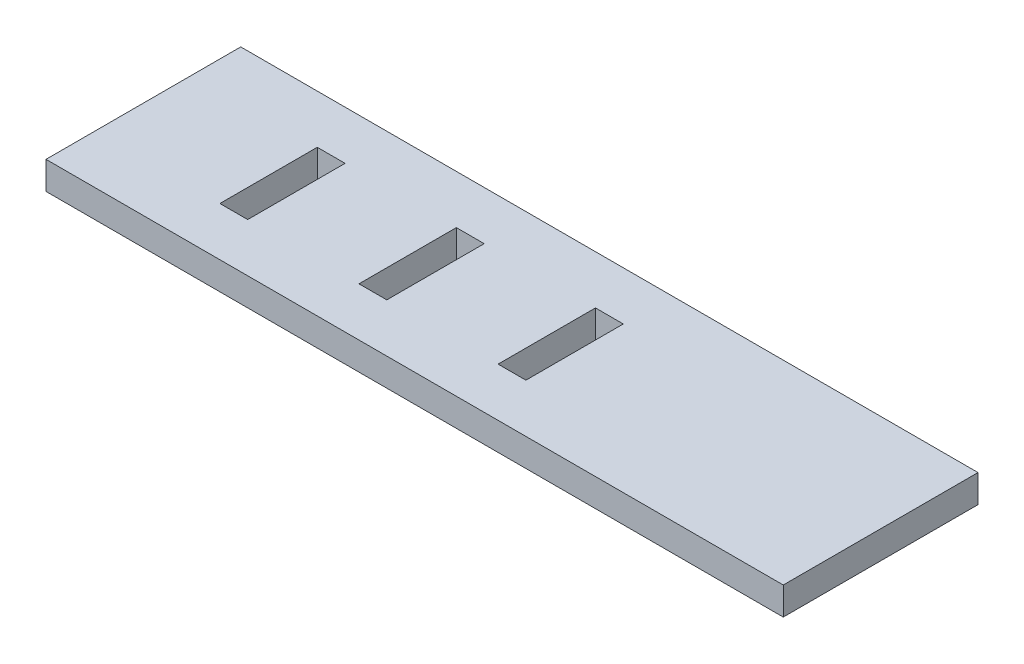
SolidWorks part; units mm, degrees
ref_plane "Front Plane" through (0, 0, 0) normal (0, 0, 1) x (1, 0, 0)
ref_plane "Top Plane" through (0, 0, 0) normal (0, 1, 0) x (1, 0, 0)
ref_plane "Right Plane" through (0, 0, 0) normal (1, 0, 0) x (0, 0, -1)
sketch "Sketch1" plane through (0, 0, 0) normal (0, 1, 0) x (1, 0, 0)
  line L0 (-98.4247, 5.9932) -> (-48.4247, 5.9932) construction
  line L1 (-98.4247, 40.9932) -> (166.5753, 40.9932)
  line L2 (-98.4247, 40.9932) -> (-98.4247, -29.0068)
  line L3 (-98.4247, -29.0068) -> (166.5753, -29.0068)
  line L4 (166.5753, 40.9932) -> (166.5753, -29.0068)
  line L5 (-98.4247, 5.9932) -> (1.5753, 5.9932) construction
  line L6 (-53.4247, 23.4932) -> (-43.4247, 23.4932)
  line L7 (-53.4247, 23.4932) -> (-53.4247, -11.5068)
  line L8 (-53.4247, -11.5068) -> (-43.4247, -11.5068)
  line L9 (-43.4247, 23.4932) -> (-43.4247, -11.5068)
  line L10 (-53.4247, 23.4932) -> (-43.4247, -11.5068) construction
  line L11 (-53.4247, -11.5068) -> (-43.4247, 23.4932) construction
  line L12 (-98.4247, 5.9932) -> (54.9772, 5.9932) construction
  line L13 (6.5753, 23.4932) -> (-3.4247, 23.4932)
  line L14 (6.5753, 23.4932) -> (6.5753, -11.5068)
  line L15 (6.5753, -11.5068) -> (-3.4247, -11.5068)
  line L16 (-3.4247, 23.4932) -> (-3.4247, -11.5068)
  line L17 (6.5753, 23.4932) -> (-3.4247, -11.5068) construction
  line L18 (6.5753, -11.5068) -> (-3.4247, 23.4932) construction
  line L21 (46.5753, 23.4932) -> (56.5753, 23.4932)
  line L22 (46.5753, 23.4932) -> (46.5753, -11.5068)
  line L23 (46.5753, -11.5068) -> (56.5753, -11.5068)
  line L24 (56.5753, 23.4932) -> (56.5753, -11.5068)
  line L25 (46.5753, 23.4932) -> (56.5753, -11.5068) construction
  line L26 (46.5753, -11.5068) -> (56.5753, 23.4932) construction
  dimension "D1" = 70
  dimension "D2" = 265
  dimension "D3" = 50
  dimension "D4" = 10
  dimension "D5" = 35
  dimension "D6" = 100
  dimension "D7" = 10
  dimension "D9" = 10
extrude "Boss-Extrude1" add sketch "Sketch1" along normal blind 10
